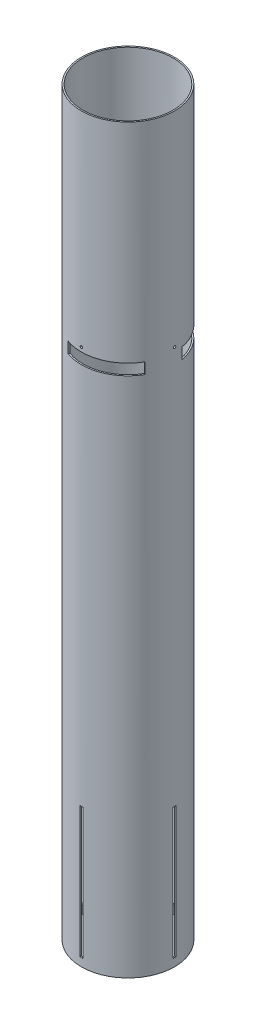
SolidWorks part; units mm, degrees
material "A-Glass Fiber"
ref_plane "Front Plane" through (0, 0, 0) normal (0, 0, 1) x (1, 0, 0)
ref_plane "Top Plane" through (0, 0, 0) normal (0, 1, 0) x (1, 0, 0)
ref_plane "Right Plane" through (0, 0, 0) normal (1, 0, 0) x (0, 0, -1)
sketch "Sketch1" plane through (0, 0, 0) normal (0, 1, 0) x (1, 0, 0)
  circle A0 centre (0, 0) radius 49.53
  circle A1 centre (0, 0) radius 51.1048
  dimension "D1" = 99.06
  dimension "D2" = 102.2096
extrude "Boss-Extrude1" add sketch "Sketch1" along normal blind 812.8
ref_plane "Plane1" through (0, 0, 0) normal (0.7071, 0, 0.7071) x (0.7071, 0, -0.7071)
ref_axis "Axis1" through (0, 812.8, 0) along (0, -1, 0)
sketch "Sketch2" plane through (0, 0, 0) normal (1, 0, 0) x (0, 0, -1)
  line L0 (0, 0) -> (0, 8.89)
  line L1 (1.5875, 8.89) -> (-1.5875, 8.89)
  line L2 (1.5875, 8.89) -> (1.5875, 152.4)
  line L3 (1.5875, 152.4) -> (-1.5875, 152.4)
  line L4 (-1.5875, 8.89) -> (-1.5875, 152.4)
  line L5 (1.5875, 8.89) -> (-1.5875, 152.4) construction
  line L6 (1.5875, 152.4) -> (-1.5875, 8.89) construction
  line L7 (51.1048, 812.8) -> (-51.1048, 812.8) construction
  line L8 (51.1048, 812.8) -> (-51.1048, 812.8)
  line L9 (0, 812.8) -> (0, 588.645)
  line L10 (-51.1048, 0) -> (51.1048, 0) construction
  circle A0 centre (0, 588.645) radius 1.3525
  point P0 (0, 80.645)
  dimension "D4" = 2.7051
  dimension "D1" = 3.175
  dimension "D5" = 588.645
  dimension "D3" = 152.4
  dimension "D2" = 8.89
extrude "Cut-Extrude1" cut sketch "Sketch2" against normal through all contours L4 L1 L2 L3 region at (0, 80.645, 0)
pattern_circular "CirPattern1" count 4 over 360 about axis through (0, 0, 0) along (0, 1, 0) of "Cut-Extrude1" reverse direction yes
extrude "Cut-Extrude2" cut sketch "Sketch2<3>" against normal through all contours A0 region at (0, 587.7157, 0.9293)
sketch "Sketch2<3>" plane through (0, 0, 0) normal (1, 0, 0) x (0, 0, -1) same geometry as "Sketch2"
pattern_circular "CirPattern2" count 4 over 360 about axis through (0, 812.8, 0) along (0, -1, 0) of "Cut-Extrude2"
sketch "Sketch3" plane through (0, 0, 0) normal (0.7071, 0, 0.7071) x (0.7071, 0, -0.7071)
  line L0 (0, 0) -> (0, 127) construction
  circle A0 centre (0, 127) radius 3.175
  dimension "D1" = 6.35
  dimension "D2" = 127
extrude "Cut-Extrude3" cut sketch "Sketch3" against normal through all
ref_plane "Plane3" through (0, 583.8825, 0) normal (0, 1, 0) x (1, 0, 0)
sketch "Sketch7" plane through (0, 583.8825, 0) normal (0, 1, 0) x (1, 0, 0)
  line L0 (0, 0) -> (-44.2581, -25.5524)
  line L1 (0, 0) -> (0, 93.232) construction
  line L2 (0, 0) -> (-32.8495, 39.1485)
  line L3 (-51.1048, 0) -> (0, 0) construction
  arc A0 (-51.0869, 1.3526) -> (-51.0869, -1.3525) centre (0, 0) ccw construction
  circle A1 centre (0, 0) radius 49.53 construction
  circle A2 centre (0, 0) radius 51.1048
  circle A3 centre (0, 0) radius 51.1048
  circle A4 centre (0, 0) radius 49.53
  circle A5 centre (0, 0) radius 51.1048 construction
  arc A6 (1.3526, 51.0869) -> (-1.3525, 51.0869) centre (0, 0) ccw construction
  arc A7 (-51.0869, 1.3526) -> (-51.0869, -1.3525) centre (0, 0) ccw
  arc A8 (1.3526, 51.0869) -> (-1.3525, 51.0869) centre (0, 0) ccw
  dimension "D1" = 80
  dimension "D3" = 30
  dimension "D2" = 0
extrude "Cut-Extrude4" cut sketch "Sketch7" against normal blind 12.065 contours A4 A3 L0 region at (-43.9137, 583.8825, 24.5741)
pattern_circular "CirPattern3" count 3 over 360 about axis through (0, 812.8, 0) along (0, -1, 0) of "Cut-Extrude4"
equation "\"D1@Boss-Extrude1\" = \"Aft_Section_Length\""
equation "\"AB_Coupler_OD_Length\"= 1in"
equation "\"AB_Coupling_Section_Length\"= 0.375in"
equation "\"AB_Coupler_Length\"= \"AB_Coupler_OD_Length\" + \"AB_Coupling_Section_Length\" * 2"
equation "\"AB_Coupler_Num_Screws\"= 4"
equation "\"AB_Coupling_Screw_Diameter\"= 0.1065in"
equation "\"Aft_Section_Length\" = 32in"
equation "\"D4@Sketch2\"=\"AB_Coupling_Screw_Diameter\""
equation "\"D1@CirPattern2\"=\"AB_Coupler_Num_Screws\""
equation "\"Rail_Nut_From_Bottom\"= 5in"
equation "\"Rail_Nut_Diam\"= 0.25in"
equation "\"D1@Sketch3\"=\"Rail_Nut_Diam\""
equation "\"D2@Sketch3\"=\"Rail_Nut_From_Bottom\""
equation "\"AB_BKHD_Thickness\"= 0.375in"
equation "\"AB_Mount_From_Bottom\"= 23.175in"
equation "\"Cutout_Angle\" = 60"
equation "\"Motor_OD\" = 54.4mm"
equation "\"Motor_Length\" = 401mm"
equation "\"Mid_Coupler_Length\" = 12in"
equation "\"AB_Paddle_Height\" = 0.375in"
equation "\"Num_Cutouts\" = 4"
equation "\"AB_Coupler_OD\"= 4.024in"
equation "\"AB_Coupler_ID\"= 3.7in"
equation "\"AB_Coupler_Surface_Diameter\"= 3.899in"
equation "\"AB_Central_Bushing_Length\" = 0.75in"
equation "\"Lead_Screw_Dist\" = 2in"
equation "\"Lead_Screw_Diam\" = 0.375in"
equation "\"Lead_Screw_Length\" = \"Mid_Coupler_Length\" + 2*0.375in + 2*0.5in"
equation "\"Paddle_Pin_Offset\" = 0.25in"
equation "\"Paddle_Pin_Radius\" = 2.25*2/3in"
equation "\"Paddle_Gear_OD\" = 3.2in"
equation "\"Fwd_BKHD_From_Top\" = 18in"
equation "\"Body_Tube_OD\"= 4.024in"
equation "\"Body_Tube_ID\"= 3.90in"
equation "\"Coupler_OD\" = 3.899in"
equation "\"Coupler_ID\" = 3.755in"
equation "\"Fwd_Section_Length\" = 20in"
equation "\"Mid_Section_Length\" = 4in"
equation "\"Aft_Upper_Tube_Length\" = 10in"
equation "\"Aft_Lower_Tube_Length\" = 18in"
equation "\"Nosecone_Coupler_Length\" = 5in"
equation "\"Avionics_Bulkhead_Thickness\" = 0.25in"
equation "\"Avionics_Bulkhead_Lip\" = 0.125in"
equation "\"Avionics_Board_Length\" = \"Mid_Coupler_Length\" - 2*\"Avionics_Bulkhead_Lip\""
equation "\"Lead_Screw_Hole_Diam\" = 0.386in"
equation "\"Centering_Ring_Cutout_Dia\"=1.5in"
equation "\"D2@Sketch1\"=\"Body_Tube_OD\""
equation "\"D1@Sketch1\"=\"Body_Tube_ID\""
